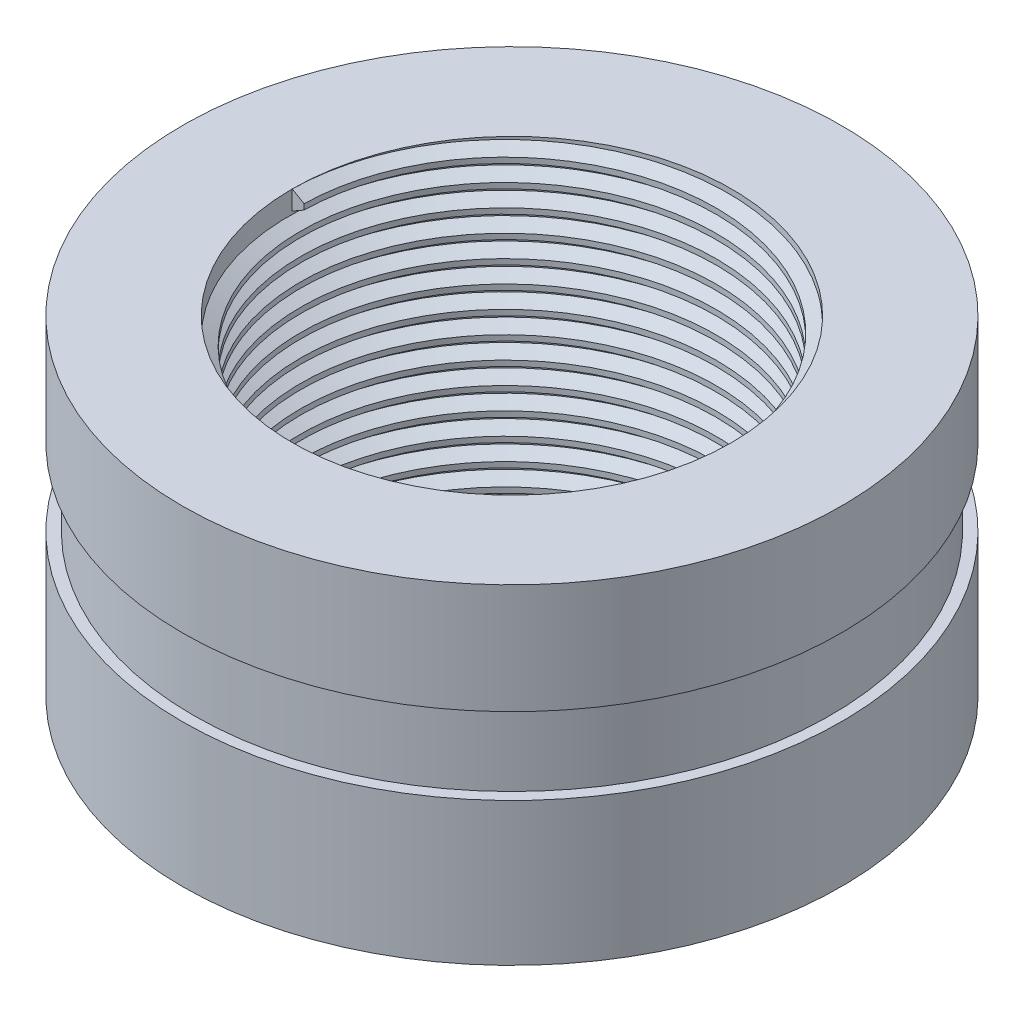
SolidWorks part; units mm, degrees
ref_plane "Front Plane" through (0, 0, 0) normal (0, 0, 1) x (1, 0, 0)
ref_plane "Top Plane" through (0, 0, 0) normal (0, 1, 0) x (1, 0, 0)
ref_plane "Right Plane" through (0, 0, 0) normal (1, 0, 0) x (0, 0, -1)
sketch "Sketch1" plane through (0, 0, 0) normal (0, 1, 0) x (1, 0, 0)
  circle A0 centre (0, 0) radius 30
  circle A1 centre (0, 0) radius 20
extrude "Boss-Extrude1" add sketch "Sketch1" along normal blind 30 contours A1 | A0 region at (0, 0, 0)
thread "Thread1" pitch 2 method extrude profile "Thread Profile2" start angle 0, offset 0, length 0, pitch 2, diameter 40
ref_plane "Plane2" through (-20, 30, 0) normal (0, 0, 1) x (-1, 0, 0)
sketch "Thread Profile2" plane through (-20, 30, 0) normal (0, 0, 1) x (-1, 0, 0)
  line L0 (0, 0) -> (0, 2) construction
  line L11 (0, 0) -> (0, 1.75)
  line L12 (0, 1.75) -> (-1.0825, 1.125)
  line L13 (-1.0825, 1.125) -> (-1.0825, 0.625)
  line L15 (-1.0825, 0.625) -> (0, 0)
  line L17 (-1.0825, 0.875) -> (0, 0.875) construction
  point P2 (0, 0)
  dimension "Pitch" = 2
  dimension "Profile_Angle" = 60
  dimension "Profile_Land" = 0.5
  dimension "Profile_Height" = 1.0825
ref_plane "Plane4" through (0, 20, 0) normal (0, 1, 0) x (1, 0, 0)
sketch "Sketch17" plane through (0, 20, 0) normal (0, 1, 0) x (1, 0, 0)
  circle A0 centre (0, 0) radius 30
  circle A1 centre (0, 0) radius 29
extrude "Cut-Extrude1" cut sketch "Sketch17" against normal blind 7 contours A0 A1 region at (-29.1515, 20, 0)
sketch "Sketch18" plane through (0, 20, 0) normal (0, 1, 0) x (1, 0, 0)
  circle A0 centre (0, 0) radius 29
  circle A1 centre (0, 0) radius 30
  arc A2 (-1.5333, 28.9594) -> (1.4904, 28.9617) centre (-0.0208, 28.1149) cw
  arc A3 (3.132, 28.8304) -> (6.1168, 28.3476) centre (4.4894, 27.7542) cw
  arc A4 (7.7161, 27.9546) -> (10.5849, 26.9993) centre (8.8833, 26.6747) cw
  arc A5 (12.1004, 26.3549) -> (14.7788, 24.9517) centre (13.0472, 24.9042) cw
  arc A6 (16.1714, 24.0725) -> (18.59, 22.2579) centre (16.8732, 22.4888) cw
  arc A7 (19.8235, 21.1667) -> (21.9196, 18.9876) centre (20.2621, 19.4909) cw
  arc A8 (22.9621, 17.7127) -> (24.6816, 15.2256) centre (23.1263, 15.9883) cw
  arc A9 (25.5061, 13.8) -> (26.8043, 11.0692) centre (25.3915, 12.0715) cw
  arc A10 (27.3895, 9.5298) -> (28.2329, 6.6261) centre (26.9991, 7.8421) cw
  arc A11 (28.5635, 5.0128) -> (28.9302, 2.0115) centre (27.9074, 3.4096) cw
  arc A12 (28.9977, 0.366) -> (28.8782, -2.6553) centre (28.093, -1.1112) cw
  arc A13 (28.6809, -4.2903) -> (28.0783, -7.2533) centre (27.5509, -5.6033) cw
  arc A14 (27.6213, -8.8355) -> (26.5512, -11.6635) centre (26.2953, -9.9502) cw
  arc A15 (25.8463, -13.1518) -> (24.3364, -15.7715) centre (24.3587, -14.0394) cw
  arc A16 (23.4019, -17.1276) -> (21.4913, -19.4711) centre (21.7912, -17.765) cw
  arc A17 (20.3514, -20.6597) -> (18.0896, -22.6664) centre (18.6593, -21.0305) cw
  arc A18 (16.7738, -23.6567) -> (14.2194, -25.2747) centre (15.0441, -23.7513) cw
  arc A19 (12.7617, -26.0411) -> (9.9809, -27.2283) centre (11.0393, -25.857) cw
  arc A20 (8.4192, -27.751) -> (5.4839, -28.4768) centre (6.7486, -27.293) cw
  arc A21 (3.8586, -28.7422) -> (0.8449, -28.9877) centre (2.2831, -28.0221) cw
  arc A22 (-0.8019, -28.9889) -> (-3.816, -28.7478) centre (-2.2415, -28.0255) cw
  arc A23 (-5.4417, -28.4849) -> (-8.378, -27.7634) centre (-6.7081, -27.303) cw
  arc A24 (-9.9405, -27.2431) -> (-12.7231, -26.06) centre (-11.0009, -25.8733) cw
  arc A25 (-14.1819, -25.2957) -> (-16.7387, -23.6816) centre (-15.0089, -23.7736) cw
  arc A26 (-18.056, -22.6932) -> (-20.3207, -20.6898) centre (-18.6281, -21.0582) cw
  arc A27 (-21.4624, -19.503) -> (-23.3764, -17.1622) centre (-21.7648, -17.7973) cw
  arc A28 (-24.313, -15.8076) -> (-25.8267, -13.1902) centre (-24.3378, -14.0755) cw
  arc A29 (-26.5338, -11.7028) -> (-27.6081, -8.8764) centre (-26.2805, -9.9892) cw
  arc A30 (-28.0675, -7.2949) -> (-28.6745, -4.3328) centre (-27.5426, -5.6441) cw
  arc A31 (-28.8742, -2.6981) -> (-28.9982, 0.323) centre (-28.0913, -1.1529) cw
  arc A32 (-28.9331, 1.9685) -> (-28.5709, 4.9704) centre (-27.9125, 3.3682) cw
  arc A33 (-28.2427, 6.5843) -> (-27.4036, 9.4892) centre (-27.0107, 7.802) cw
  arc A34 (-26.8207, 11.0294) -> (-25.5265, 13.7621) centre (-25.4094, 12.0338) cw
  arc A35 (-24.7042, 15.189) -> (-22.9884, 17.6786) centre (-23.15, 15.954) cw
  arc A36 (-21.9478, 18.9551) -> (-19.8548, 21.1373) centre (-20.291, 19.4609) cw
  arc A37 (-18.6229, 22.2303) -> (-16.2071, 24.0485) centre (-16.9065, 22.4638) cw
  arc A38 (-14.8158, 24.9297) -> (-12.1395, 26.3369) centre (-13.0841, 24.8849) cw
  arc A39 (-10.6249, 26.9835) -> (-7.7576, 27.9432) centre (-8.9229, 26.6614) cw
  arc A40 (-6.1589, 28.3385) -> (-3.1747, 28.8257) centre (-4.5305, 27.7475) cw
  point P123 (0, 0)
  dimension "D1" = 39
